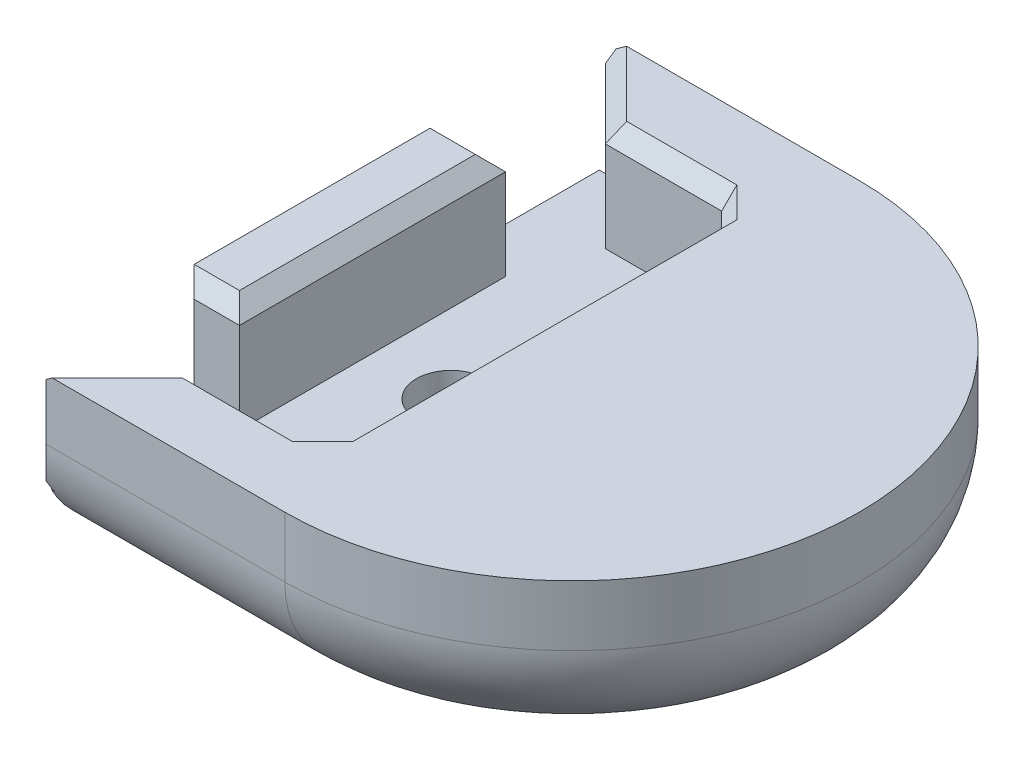
SolidWorks part; units mm, degrees
other "Markup1"
sketch "Sketch13" plane through (9.5, -5.9248, 9.5) normal (0.1837, -0.9341, 0.306) x (0.0497, 0.3198, 0.9462)
ref_plane "Front Plane" through (0, 0, 0) normal (0, 0, 1) x (1, 0, 0)
ref_plane "Top Plane" through (0, 0, 0) normal (0, 1, 0) x (1, 0, 0)
ref_plane "Right Plane" through (0, 0, 0) normal (1, 0, 0) x (0, 0, -1)
sketch "Sketch1" plane through (0, 0, 0) normal (0, 1, 0) x (1, 0, 0)
  line L0 (0, 0) -> (8099.319, 0) construction
  line L1 (0, 0) -> (0, 8099.319) construction
  line L2 (-8.6, -4.5) -> (-8.6, 4.5)
  line L3 (0, 9.5) -> (-8.6, 9.5)
  line L4 (-8.6, 9.5) -> (-8.6, 4.5)
  line L5 (0, -9.5) -> (-8.6, -9.5)
  line L6 (-8.6, -9.5) -> (-8.6, -4.5)
  line L7 (0, 0) -> (9.5, 0) construction
  arc A0 (0, -9.5) -> (0, 9.5) centre (0, 0) ccw
  arc A1 (-8.6, 4.0361) -> (-9.5, 0) centre (0, 0) ccw construction
  arc A2 (-9.5, 0) -> (-8.6, -4.0361) centre (0, 0) ccw construction
  arc A3 (-8.6, -4.0361) -> (0, -9.5) centre (0, 0) ccw construction
  arc A4 (0, 9.5) -> (-8.6, 4.0361) centre (0, 0) ccw construction
  point P8 (-8.6, 0)
  dimension "D2" = 19
  dimension "D1" = 9
  dimension "D3" = 18.1
extrude "Boss-Extrude1" add sketch "Sketch1" against normal blind 2
sketch "Sketch2" plane through (0, 0, 0) normal (0, 1, 0) x (1, 0, 0)
  line L0 (-8.6, 9.5) -> (-8.6, -9.5) construction
  line L1 (-8.6, 4.4) -> (-6.6, 4.4)
  line L2 (-8.6, 4.4) -> (-8.6, 0)
  line L3 (-8.6, 0) -> (-6.6, 0) construction
  line L4 (-6.6, 4.4) -> (-6.6, -4.4)
  line L5 (0, 0) -> (-8.6, 0) construction
  line L6 (-8.4, 9.5) -> (-5.75, 6.85)
  line L7 (-5.75, 6.85) -> (-1.4, 6.85)
  line L8 (-8.4, 9.5) -> (0, 9.5)
  line L10 (-1.4, 6.85) -> (-1.4, -6.85)
  line L11 (-1.4, 0) -> (9.5, 0) construction
  line L12 (-5.75, -6.85) -> (-1.4, -6.85)
  line L13 (-8.4, -9.5) -> (-5.75, -6.85)
  line L14 (-8.4, -9.5) -> (0, -9.5)
  line L15 (-8.6, -4.4) -> (-6.6, -4.4)
  line L16 (-8.6, -4.4) -> (-8.6, 0)
  line L17 (0, 9.5) -> (-8.6, 9.5) construction
  arc A0 (0, -9.5) -> (0, 9.5) centre (0, 0) ccw construction
  arc A1 (0, -9.5) -> (0, 9.5) centre (0, 0) ccw
  dimension "D1" = 4.4
  dimension "D2" = 2
  dimension "D3" = 2.85
  dimension "D4" = 45
  dimension "D5" = 4.35
  dimension "D6" = 0.2
extrude "Boss-Extrude2" add sketch "Sketch2" along normal blind 3.5
ref_plane "Plane1" through (0, -4.5, 0) normal (0, 1, 0) x (1, 0, 0)
sketch "Sketch4" plane through (0, 0, 0) normal (0, 1, 0) x (1, 0, 0)
  line L0 (-6.6, 0) -> (-1.4, 0) construction
  line L1 (-6.6, -4.4) -> (-6.6, 4.4) construction
  line L2 (-1.4, 6.85) -> (-1.4, -6.85) construction
  circle A0 centre (-4, 0) radius 1.15
  dimension "D1" = 2.3
extrude "Cut-Extrude1" cut sketch "Sketch4" against normal through all both and the other way through all
ref_plane "Plane2" through (-8.6, 3.5, 4.4) normal (0, 0, 1) x (1, 0, 0)
sketch "Sketch14" plane through (0, -2, 0) normal (0, -1, 0) x (1, 0, 0)
  line L0 (-5.1547, 2) -> (-2.8453, 2)
  line L1 (-2.8453, 2) -> (-1.6906, 0)
  line L2 (-1.6906, 0) -> (-2.8453, -2)
  line L3 (-2.8453, -2) -> (-5.1547, -2)
  line L4 (-5.1547, -2) -> (-6.3094, 0)
  line L5 (-6.3094, 0) -> (-5.1547, 2)
  circle A0 centre (-4, 0) radius 2.3094 construction
  dimension "D1" = 4
extrude "Cut-Extrude2" cut sketch "Sketch14" against normal blind 1
chamfer "Chamfer1" distance 0.5 angle 45 24 edges at (-7.6, 3.5, -4.4) (-6.6, 3.5, 0) (-7.6, 3.5, 4.4) (-7.075, 3.5, 8.175) (-3.575, 3.5, 6.85) (-1.4, 3.5, 0) (-3.575, 3.5, -6.85) (-7.075, 3.5, -8.175) (-1.4, 1.75, 6.85) (-1.4, 1.75, -6.85) (-8.6, 0, 6.95) (-8.5, 0, 9.5) (-8.4, 1.75, 9.5) (-8.5, 0, -9.5) (-8.6, 0, -6.95) (-8.4, 1.75, -9.5) (-2.2679, -2, 1) (-2.2679, -2, -1) (-4, -2, -2) (-5.7321, -2, -1) (-5.7321, -2, 1) (-4, -2, 2) (-8.6, 1.75, 4.4) (-8.6, 1.75, -4.4)
fillet "Fillet1" radius 3.5 3 edges at (-4.3, -2, 9.5) (-4.3, -2, -9.5) (9.5, -2, 0)
chamfer "Chamfer2" distance 0.5 angle 45 3 edges at (-8.6, -1.6024, -7.6202) (-8.6, -1.6024, 7.6202) (-8.6, -2, 0)
